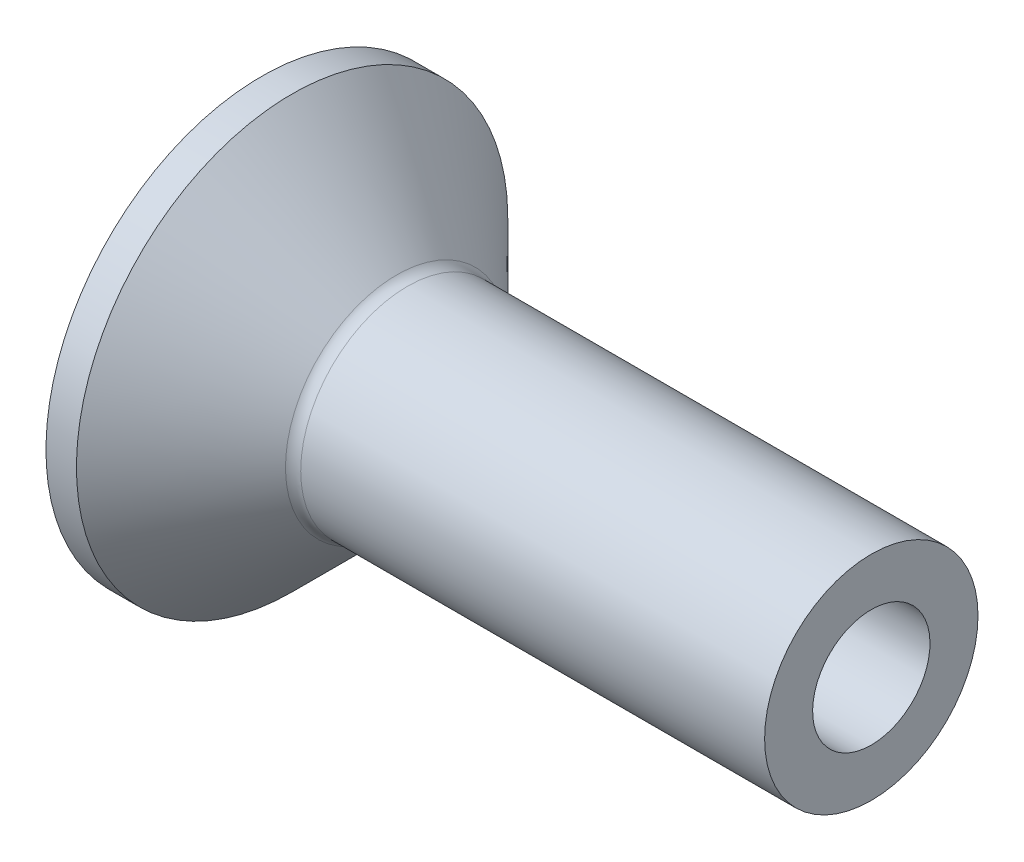
SolidWorks part; units mm, degrees
ref_plane "Front" through (0, 0, 0) normal (0, 0, 1) x (1, 0, 0)
ref_plane "Top" through (0, 0, 0) normal (0, 1, 0) x (1, 0, 0)
ref_plane "Right" through (0, 0, 0) normal (1, 0, 0) x (0, 0, -1)
sketch "Sketch1" plane through (-0.2925, -1.7075, 0) normal (0, 0, 1) x (0, 1, 0)
  line L0 (1.7075, -0.2925) -> (3.1225, -0.2925)
  line L1 (3.1225, -0.2925) -> (3.1225, -0.4925)
  line L2 (3.1225, -0.4925) -> (2.4075, -1.2075)
  line L3 (2.4075, -1.2075) -> (2.4075, -4.2925)
  line L4 (2.4075, -4.2925) -> (1.7075, -4.2925)
  line L5 (1.7075, -4.2925) -> (1.7075, -0.2925)
  line L6 (1.7075, 2.03) -> (1.7075, -4.03) construction
  dimension "b" = 0.2
  dimension "dk" = 2.83
  dimension "l" = 4
  dimension "d" = 1.4
  dimension "a" = 45
revolve "Base-Revolve" add sketch "Sketch1" angle 360 about L6
fillet "Fillet1" radius 0.1 1 edges at (0.915, -0.7, 0)
sketch "Sketch2" plane through (-3.0606, -3.4456, 0) normal (0, 0, 1) x (0, 1, 0)
  line L0 (3.4456, -1.8755) -> (3.4456, -4.6308) construction
  line L2 (3.4456, -5.6209) -> (3.8306, -5.9006)
  line L3 (3.8306, -5.9006) -> (3.8306, -7.0606)
  line L5 (3.8306, -7.0606) -> (3.4456, -7.0606)
  line L6 (3.4456, -5.6209) -> (3.4456, -7.0606)
  line L7 (2.7456, -7.0606) -> (4.1456, -7.0606) construction
  dimension "dt" = 0.77
  dimension "D2" = 54
  dimension "t" = 1.16
revolve "Cut-Revolve1" cut sketch "Sketch2" angle 360 about L0
